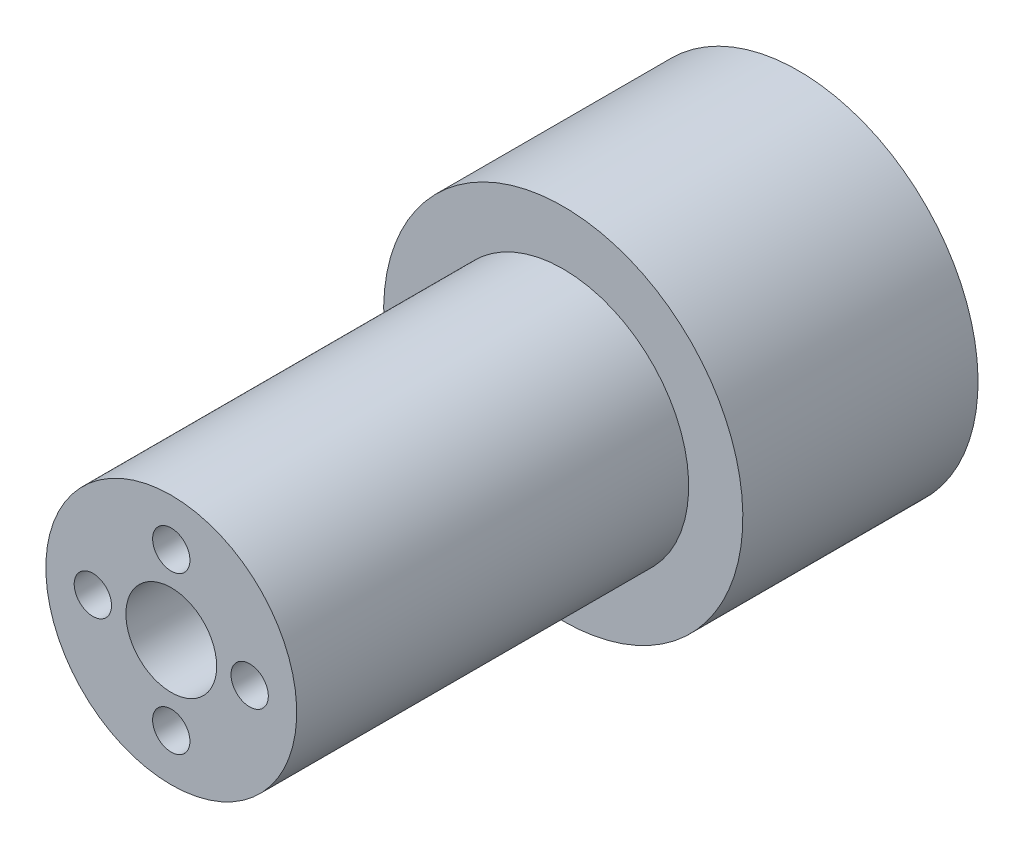
SolidWorks part; units mm, degrees
material "AISI 316 Annealed Stainless Steel Bar (SS)"
ref_plane "Front Plane" through (0, 0, 0) normal (1, 0, 0) x (0, 1, 0)
ref_plane "Top Plane" through (0, 0, 0) normal (0, 0, 1) x (0, 1, 0)
ref_plane "Right Plane" through (0, 0, 0) normal (0, 1, 0) x (-1, 0, 0)
sketch "Sketch2" plane through (0, 0, 0) normal (1, 0, 0) x (0, 1, 0)
  line L0 (0, 0) -> (0, -40)
  line L2 (0, -40) -> (11.455, -40)
  line L3 (11.455, -40) -> (11.455, -25)
  line L4 (11.455, -25) -> (8, -25)
  line L5 (8, -25) -> (8, 0)
  line L7 (8, 0) -> (0, 0)
  point P3 (0, -41.5865)
  point P10 (0, 0)
  point P11 (0, -4.0812)
  point P12 (0, 0)
  point P13 (10.2019, -40)
  point P14 (0, 0)
  point P16 (0, 0)
  point P17 (0, 0)
  point P18 (0, 0)
  point P19 (0, 0)
  point P20 (0, 0)
  dimension "D1" = 8
  dimension "D2" = 15
  dimension "D3" = 11.455
  dimension "D4" = 40
sketch "Sketch1" plane through (0, 0, 0) normal (0, 0, 1) x (0, 1, 0)
  line L0 (0, 5) -> (0, -5) construction
  line L1 (-5, 0) -> (5, 0) construction
  circle A0 centre (0, 0) radius 11.455
  circle A1 centre (0, 0) radius 2.8956
  circle A2 centre (0, 5) radius 1.1906
  circle A3 centre (-5, 0) radius 1.1906
  circle A4 centre (5, 0) radius 1.1906
  circle A5 centre (0, -5) radius 1.1906
  dimension "D1" = 22.91
  dimension "D2" = 5.7912
  dimension "D3" = 2.3812
  dimension "D4" = 10
revolve "Revolve1" add sketch "Sketch2" angle 360 about L0
extrude "Cut-Extrude1" cut sketch "Sketch1<3>" against normal blind 8 contours A2 | A3 | A4 | A5 region at (-5, 0, 0) region at (0, -5, 0) region at (0, 5, 0) region at (5, 0, 0)
sketch "Sketch1<3>" plane through (0, 0, 0) normal (0, 0, 1) x (0, 1, 0) same geometry as "Sketch1"
extrude "Cut-Extrude2" cut sketch "Sketch1" against normal blind 16 contours A1 region at (0, 0, 0)
